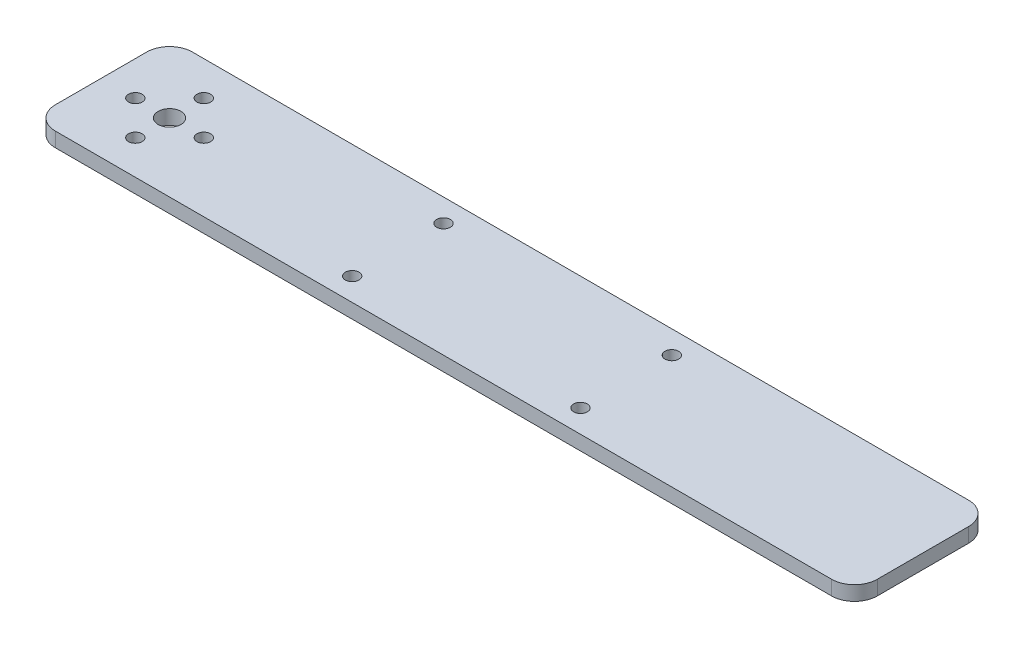
SolidWorks part; units mm, degrees
ref_plane "Front Plane" through (0, 0, 0) normal (0, 0, 1) x (1, 0, 0)
ref_plane "Top Plane" through (0, 0, 0) normal (0, 1, 0) x (1, 0, 0)
ref_plane "Right Plane" through (0, 0, 0) normal (1, 0, 0) x (0, 0, -1)
sketch "Sketch1" plane through (0, 0, 0) normal (0, 1, 0) x (1, 0, 0)
  line L1 (-15, 15) -> (165, 15)
  line L2 (-15, 15) -> (-15, -15)
  line L3 (-15, -15) -> (165, -15)
  line L4 (165, 15) -> (165, -15)
  point P4 (-15, 0)
  dimension "D1" = 180
  dimension "D2" = 30
  dimension "D3" = 15
extrude "Boss-Extrude1" add sketch "Sketch1" along normal blind 3.175
fillet "Fillet1" radius 5 4 edges at (165, 1.5875, 15) (165, 1.5875, -15) (-15, 1.5875, -15) (-15, 1.5875, 15)
sketch "Sketch2" plane through (0, 3.175, 0) normal (0, 1, 0) x (1, 0, 0)
  circle A6 centre (0, 0) radius 2.5
  dimension "D6" = 5
extrude "Cut-Extrude1" cut sketch "Sketch2" against normal through all
sketch "Sketch3" plane through (0, 3.175, 0) normal (0, 1, 0) x (1, 0, 0)
  line L0 (-15, 10) -> (-15, -10) construction
  circle A4 centre (7.5, 0) radius 1.5
  circle A5 centre (0, 0) radius 2.5 construction
  circle A6 centre (0, -7.5) radius 1.5
  circle A7 centre (-7.5, 0) radius 1.5
  circle A8 centre (0, 7.5) radius 1.5
  point P7 (-15, 0)
  dimension "D1" = 7.5
  dimension "D2" = 3
  dimension "D3" = 15
extrude "Cut-Extrude3" cut sketch "Sketch3" against normal through all
sketch "Sketch4" plane through (0, 3.175, 0) normal (0, 1, 0) x (1, 0, 0)
  line L0 (-15, 0) -> (165, 0) construction
  line L1 (-15, 10) -> (-15, -10) construction
  line L2 (165, -10) -> (165, 10) construction
  line L3 (75, 15) -> (75, -15) construction
  line L4 (160, 15) -> (-10, 15) construction
  line L5 (-10, -15) -> (160, -15) construction
  circle A0 centre (50, -10) radius 1.5
  circle A1 centre (100, -10) radius 1.5
  circle A2 centre (100, 10) radius 1.5
  circle A3 centre (50, 10) radius 1.5
  dimension "D3" = 3
  dimension "D1" = 25
  dimension "D2" = 5
extrude "Cut-Extrude4" cut sketch "Sketch4" against normal blind 10
